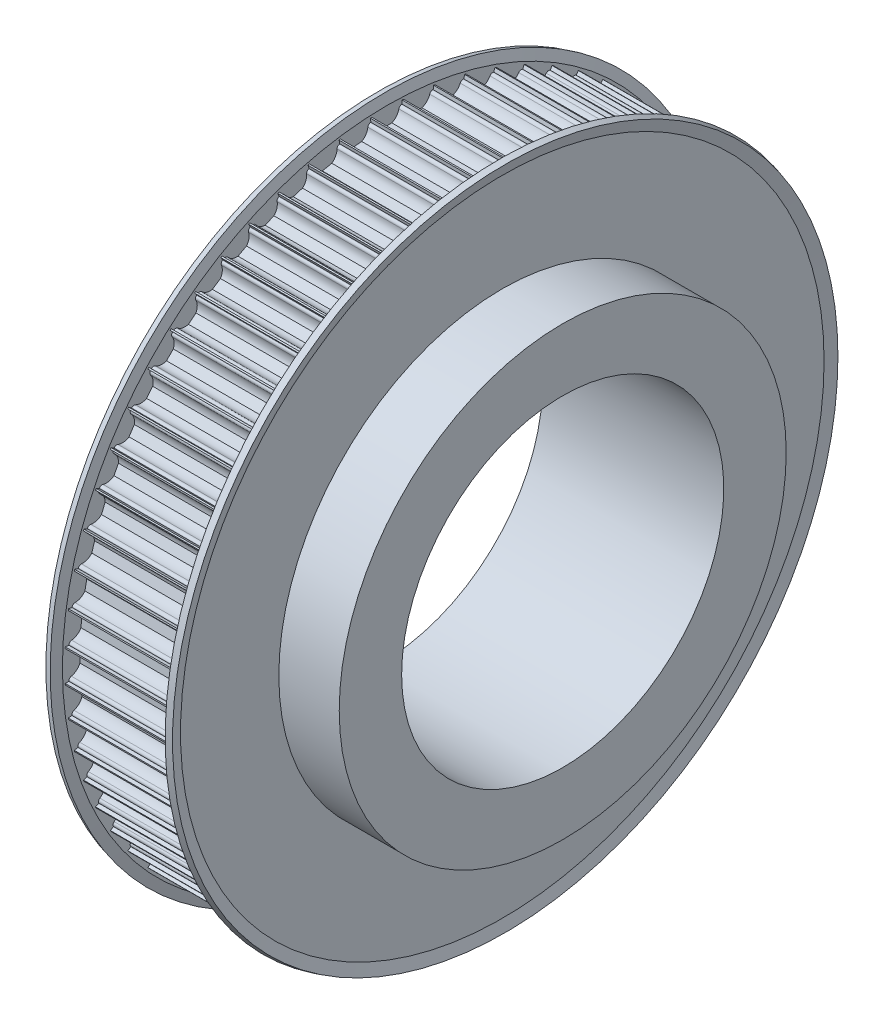
SolidWorks part; units mm, degrees
ref_plane "Front Plane" through (0, 0, 0) normal (0, 0, 1) x (1, 0, 0)
ref_plane "Top Plane" through (0, 0, 0) normal (0, 1, 0) x (1, 0, 0)
ref_plane "Right Plane" through (0, 0, 0) normal (1, 0, 0) x (0, 0, -1)
sketch "Sketch2" plane through (0, 0, 0) normal (0, 0, 1) x (1, 0, 0)
  line L0 (0, 0) -> (15.1167, 0) construction
  line L1 (0, 40) -> (0, 80)
  line L2 (0, 80) -> (30, 80)
  line L3 (30, 80) -> (30, 55.5)
  line L4 (30, 55.5) -> (45, 55.5)
  line L5 (45, 55.5) -> (45, 40)
  line L6 (45, 40) -> (0, 40)
  dimension "D1" = 40
  dimension "D2" = 80
  dimension "D3" = 30
  dimension "D4" = 15
  dimension "D5" = 15.5
revolve "Revolve1" add sketch "Sketch2" angle 360 about L0
sketch "Sketch3" plane through (0, 0, 0) normal (-1, 0, 0) x (0, 0, 1)
  line L0 (-3.6742, 79) -> (-3.75, 79)
  line L1 (-3.75, 79) -> (-3.75, 81)
  line L2 (-3.75, 81) -> (3.75, 81)
  line L3 (3.75, 81) -> (3.75, 79)
  line L4 (3.75, 79) -> (3.6742, 79)
  line L5 (-1.199, 76.25) -> (1.199, 76.25)
  arc A0 (-2.9394, 78.4) -> (-1.199, 76.25) centre (0, 79) ccw
  arc A1 (-2.9394, 78.4) -> (-3.6742, 79) centre (-3.6742, 78.25) ccw
  arc A2 (2.9394, 78.4) -> (3.6742, 79) centre (3.6742, 78.25) cw
  arc A3 (1.199, 76.25) -> (2.9394, 78.4) centre (0, 79) ccw
  point P6 (0, 81)
  point P11 (-3, 79)
  point P14 (3, 79)
  dimension "D2" = 3
  dimension "D5" = 0.75
  dimension "D6" = 0.75
  dimension "D1" = 79
  dimension "D3" = 2
  dimension "D4" = 7.5
  dimension "D7" = 2.75
extrude "Cut-Extrude1" cut sketch "Sketch3" against normal through all
pattern_circular "CirPattern1" count 64 over 360 about axis through (0, 0, 0) along (-1, 0, 0) of "Cut-Extrude1"
sketch "Sketch4" plane through (0, 0, 0) normal (0, 0, 1) x (1, 0, 0)
  line L0 (30, 55.5) -> (28.6347, 55.5)
  line L1 (28.6347, 55.5) -> (28.6347, 80.61)
  line L2 (28.6347, 80.61) -> (29.2778, 83.01)
  line L3 (29.2778, 83.01) -> (30.7267, 82.6218)
  line L4 (30.7267, 82.6218) -> (30, 79.9098)
  line L5 (30, 79.9098) -> (30, 55.5)
  line L6 (15, -40.9775) -> (15, -5.6808) construction
  line L7 (0, -40.9775) -> (30, -40.9775) construction
  line L8 (0, 55.5) -> (1.3653, 55.5)
  line L9 (0, 79.9098) -> (0, 55.5)
  line L10 (-0.7267, 82.6218) -> (0, 79.9098)
  line L11 (0.7222, 83.01) -> (-0.7267, 82.6218)
  line L12 (1.3653, 80.61) -> (0.7222, 83.01)
  line L13 (1.3653, 55.5) -> (1.3653, 80.61)
  line L14 (0, 0) -> (-20.6757, 0) construction
  dimension "D1" = 15
  dimension "D2" = 1.5
  dimension "D3" = 2.4
  dimension "D4" = 25.11
revolve "Revolve2" add sketch "Sketch4" angle 360 about L14
